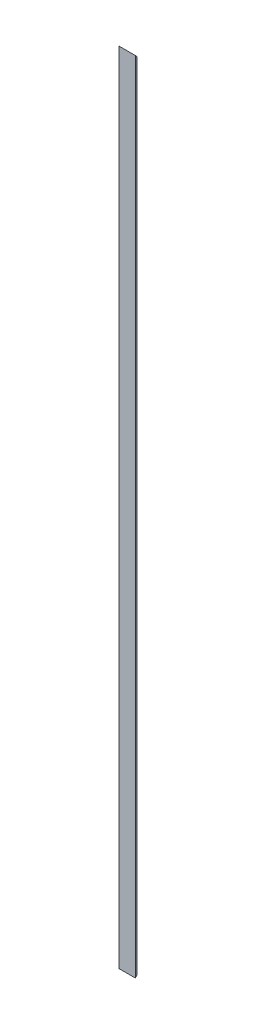
SolidWorks part; units mm, degrees
ref_plane "Спереди" through (0, 0, 0) normal (0, 0, 1) x (1, 0, 0)
ref_plane "Сверху" through (0, 0, 0) normal (0, 1, 0) x (1, 0, 0)
ref_plane "Справа" through (0, 0, 0) normal (1, 0, 0) x (0, 0, -1)
sketch "Эскиз1" plane through (0, 0, 0) normal (0, 1, 0) x (1, 0, 0)
  line L0 (0, 45) -> (0, 0)
  line L1 (0, 0) -> (45, 0)
extrude "Вытянуть-Тонкостенный1" add sketch "Эскиз1" along normal blind 2200 thin thin type one direction reverse wall 5
sketch "Эскиз2" plane through (0, 0, 0) normal (-1, 0, 0) x (0, 0, 1)
  line L0 (0, 0) -> (-45, 45)
  line L1 (-45, 2200) -> (-45, 0) construction
  line L2 (-45, 45) -> (-45, 0)
  line L3 (-45, 0) -> (0, 0)
  line L4 (0, 1100) -> (-53.7622, 1100) construction
  line L5 (0, 2200) -> (0, 0) construction
  line L6 (-45, 2200) -> (0, 2200)
  line L7 (-45, 2155) -> (-45, 2200)
  line L8 (0, 2200) -> (-45, 2155)
extrude "Вырез-Вытянуть1" cut sketch "Эскиз2" against normal through all
